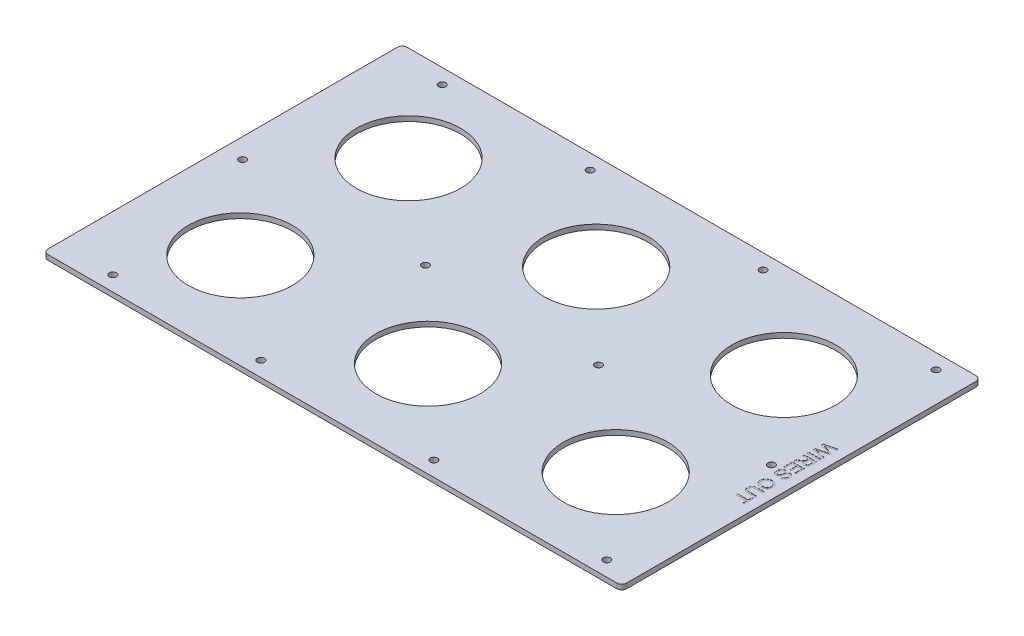
SolidWorks part; units mm, degrees
material "ABS"
ref_plane "Front" through (0, 0, 0) normal (0, 0, 1) x (1, 0, 0)
ref_plane "Top" through (0, 0, 0) normal (0, 1, 0) x (1, 0, 0)
ref_plane "Right" through (0, 0, 0) normal (1, 0, 0) x (0, 0, -1)
sketch "Sketch1" plane through (0, 0, 0) normal (0, 1, 0) x (1, 0, 0)
  line L1 (-180.975, 114.3) -> (180.975, 114.3)
  line L2 (-184.15, 111.125) -> (-184.15, -111.125)
  line L3 (-180.975, -114.3) -> (180.975, -114.3)
  line L4 (184.15, 111.125) -> (184.15, -111.125)
  line L5 (-184.15, 114.3) -> (184.15, -114.3) construction
  line L6 (-184.15, -114.3) -> (184.15, 114.3) construction
  circle A0 centre (119.5086, -53.5178) radius 33.147
  arc A1 (-184.15, -111.125) -> (-180.975, -114.3) centre (-180.975, -111.125) ccw
  arc A2 (180.975, -114.3) -> (184.15, -111.125) centre (180.975, -111.125) ccw
  arc A3 (184.15, 111.125) -> (180.975, 114.3) centre (180.975, 111.125) ccw
  arc A4 (-180.975, 114.3) -> (-184.15, 111.125) centre (-180.975, 111.125) ccw
  circle A5 centre (165.1, 0) radius 2.2479 construction
  circle A6 centre (165.1, 0) radius 2.2479
  circle A7 centre (-171.45, 0) radius 2.2479 construction
  circle A8 centre (-171.45, 0) radius 2.2479
  circle A21 centre (-55.0333, 0) radius 2.2479 construction
  circle A22 centre (55.0333, 0) radius 2.2479 construction
  circle A23 centre (-55.0333, 0) radius 2.2479
  circle A24 centre (55.0333, 0) radius 2.2479
  circle A25 centre (119.5086, 53.5178) radius 33.147
  circle A26 centre (0.0643, 53.5178) radius 33.147
  circle A27 centre (0.0643, -53.5178) radius 33.147
  circle A28 centre (-119.38, 53.5178) radius 33.147
  circle A29 centre (-119.38, -53.5178) radius 33.147
  arc A34 (-143.7521, 103.8733) -> (-143.7521, 3.1623) centre (-119.38, 53.5178) ccw construction
  arc A35 (-24.3078, 103.8733) -> (-24.3078, 3.1623) centre (0.0643, 53.5178) ccw construction
  arc A36 (95.1365, 103.8733) -> (95.1365, 3.1623) centre (119.5086, 53.5178) ccw construction
  arc A37 (-143.7521, -3.1623) -> (-143.7521, -103.8733) centre (-119.38, -53.5178) ccw construction
  arc A38 (-24.3078, -3.1623) -> (-24.3078, -103.8733) centre (0.0643, -53.5178) ccw construction
  arc A39 (95.1365, -3.1623) -> (95.1365, -103.8733) centre (119.5086, -53.5178) ccw construction
  circle A40 centre (-149.225, -104.775) radius 2.2479 construction
  circle A41 centre (-55.0333, -104.775) radius 2.2479 construction
  circle A42 centre (55.0333, -104.775) radius 2.2479 construction
  circle A43 centre (165.1, -104.775) radius 2.2479 construction
  circle A44 centre (-149.225, 104.775) radius 2.2479 construction
  circle A45 centre (-55.0333, 104.775) radius 2.2479 construction
  circle A46 centre (55.0333, 104.775) radius 2.2479 construction
  circle A47 centre (165.1, 104.775) radius 2.2479 construction
  circle A48 centre (-149.225, -104.775) radius 2.2479
  circle A49 centre (-55.0333, -104.775) radius 2.2479
  circle A50 centre (55.0333, -104.775) radius 2.2479
  circle A51 centre (165.1, -104.775) radius 2.2479
  circle A52 centre (-149.225, 104.775) radius 2.2479
  circle A53 centre (-55.0333, 104.775) radius 2.2479
  circle A54 centre (55.0333, 104.775) radius 2.2479
  circle A55 centre (165.1, 104.775) radius 2.2479
  point P0 (0, 0)
  dimension "D3" = 66.294
  dimension "D4" = 3.175
  dimension "D1" = 368.3
  dimension "D2" = 228.6
extrude "Boss-Extrude1" add sketch "Sketch1" along normal blind 3.175
sketch "Sketch2" plane through (0, 3.175, 0) normal (0, 1, 0) x (1, 0, 0)
  line L0 (170.15, 30) -> (170.15, -30) construction
  line L1 (0, 0) -> (184.15, 0) construction
  line L2 (184.15, -111.125) -> (184.15, 111.125) construction
  text T0 "WIRES OUT" font "Arial" height in points 30
  point P7 (170.15, 0)
  dimension "D1" = 14
  dimension "D2" = 60
extrude "Cut-Extrude1" cut sketch "Sketch2" against normal blind 0.1
sketch "Sketch3" [suppressed] plane through (0, 0, 0) normal (0, 1, 0) x (1, 0, 0)
  line L0 (564.5895, -114.2759) -> (564.5895, 114.3581)
  line L1 (-186.5909, 117.2946) -> (1032.6091, 117.2946)
  line L2 (-186.5909, 117.2946) -> (-186.5909, -492.3054)
  line L3 (-186.5909, -492.3054) -> (1032.6091, -492.3054)
  line L4 (1032.6091, 117.2946) -> (1032.6091, -492.3054)
  line L5 (184.5895, -114.2759) -> (-184.2953, -114.2759)
  line L6 (184.5895, -114.2759) -> (184.5895, 114.3581)
  line L7 (184.5895, 114.3581) -> (-184.2953, 114.3581)
  line L8 (-184.2953, -114.2759) -> (-184.2953, 114.3581)
  line L9 (564.5895, -114.2759) -> (195.7047, -114.2759)
  line L10 (195.7047, -114.2759) -> (195.7047, 114.3581)
  line L11 (564.5895, 114.3581) -> (195.7047, 114.3581)
  line L12 (944.5895, -114.2759) -> (944.5895, 114.3581)
  line L13 (944.5895, -114.2759) -> (575.7047, -114.2759)
  line L14 (575.7047, -114.2759) -> (575.7047, 114.3581)
  line L15 (944.5895, 114.3581) -> (575.7047, 114.3581)
  line L16 (564.5895, -364.2759) -> (564.5895, -135.6419)
  line L17 (564.5895, -364.2759) -> (195.7047, -364.2759)
  line L18 (195.7047, -364.2759) -> (195.7047, -135.6419)
  line L19 (564.5895, -135.6419) -> (195.7047, -135.6419)
  line L20 (944.5895, -364.2759) -> (944.5895, -135.6419)
  line L21 (944.5895, -364.2759) -> (575.7047, -364.2759)
  line L22 (575.7047, -364.2759) -> (575.7047, -135.6419)
  line L23 (944.5895, -135.6419) -> (575.7047, -135.6419)
  line L24 (184.5895, -364.2759) -> (184.5895, -135.6419)
  line L25 (184.5895, -364.2759) -> (-184.2953, -364.2759)
  line L26 (-184.2953, -364.2759) -> (-184.2953, -135.6419)
  line L27 (184.5895, -135.6419) -> (-184.2953, -135.6419)
  dimension "D1" = 1219.2
  dimension "D2" = 609.6
  dimension "D3" = 3
  dimension "D4" = 2
